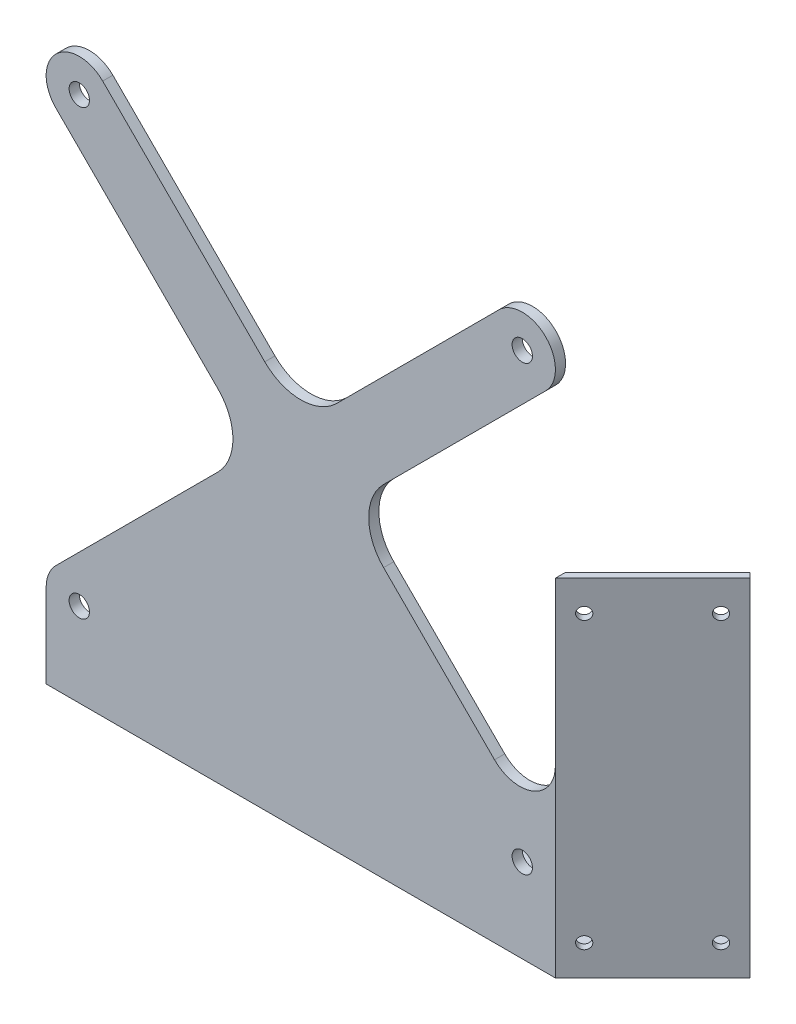
SolidWorks part; units mm, degrees
ref_plane "Plan de face" through (0, 0, 0) normal (0, 0, 1) x (1, 0, 0)
ref_plane "Plan de dessus" through (0, 0, 0) normal (0, 1, 0) x (1, 0, 0)
ref_plane "Plan de droite" through (0, 0, 0) normal (1, 0, 0) x (0, 0, -1)
sketch "Esquisse1" plane through (0, 0, 0) normal (0, 0, 1) x (1, 0, 0)
  line L1 (50, -55) -> (-50, -55)
  line L2 (50, -55) -> (50, 55)
  line L3 (50, 55) -> (-50, 55)
  line L4 (-50, -55) -> (-50, 55)
  line L5 (50, -55) -> (-50, 55) construction
  line L6 (50, 55) -> (-50, -55) construction
  point P0 (0, 0)
  dimension "D1" = 110
  dimension "D2" = 100
extrude "Boss.-Extru.1" add sketch "Esquisse1" along normal blind 2
sketch "Esquisse3" plane through (0, -55, 0) normal (0, -1, 0) x (1, 0, 0)
  line L0 (-50, 0) -> (50, 0)
  line L1 (-50, 0) -> (-50, -20)
  line L2 (50, 0) -> (50, -20)
  line L3 (-50, -20) -> (50, -20)
  dimension "D1" = 20
extrude "Boss.-Extru.2" add sketch "Esquisse3" against normal blind 3
sketch "Esquisse6" plane through (0, 0, 2) normal (0, 0, 1) x (1, 0, 0)
  line L0 (-43.5, 48.5) -> (-43.5, 55) construction
  line L1 (43.5, -38.5) -> (-43.5, -38.5) construction
  line L2 (43.5, -38.5) -> (43.5, 48.5) construction
  line L3 (43.5, 48.5) -> (-43.5, 48.5) construction
  line L4 (-43.5, -38.5) -> (-43.5, 48.5) construction
  line L5 (43.5, -38.5) -> (-43.5, 48.5) construction
  line L6 (43.5, 48.5) -> (-43.5, -38.5) construction
  line L7 (-43.5, 48.5) -> (-50, 48.5) construction
  line L8 (-50, 55) -> (-50, -55) construction
  line L9 (50, 55) -> (-50, 55) construction
  circle A0 centre (-43.5, 48.5) radius 2
  circle A1 centre (43.5, 48.5) radius 2
  circle A2 centre (-43.5, -38.5) radius 2
  circle A3 centre (43.5, -38.5) radius 2
  point P0 (0, 5)
  dimension "D1" = 4
  dimension "D2" = 87
extrude "Enlèv. mat.-Extru.1" cut sketch "Esquisse6" against normal through all
sketch "Esquisse7" plane through (0, 0, 2) normal (0, 0, 1) x (1, 0, 0)
  line L0 (-48.0962, 43.9038) -> (-9.1924, 5)
  line L1 (50, 55) -> (-50, 55) construction
  line L2 (-48.0962, -33.9038) -> (-9.1924, 5)
  line L3 (-50, 55) -> (-50, -55) construction
  line L4 (-48.0962, 43.9038) -> (-38.9038, 53.0962) construction
  line L5 (-38.9038, 53.0962) -> (0, 14.1924)
  line L6 (0, 14.1924) -> (0, 55)
  line L7 (0, 55) -> (-50, 55)
  line L8 (-50, 55) -> (-50, -38.5)
  arc A0 (-38.9038, 53.0962) -> (-48.0962, 43.9038) centre (-43.5, 48.5) ccw
  arc A1 (-48.0962, -33.9038) -> (-50, -38.5) centre (-43.5, -38.5) ccw
  line M14 (-50, 55) -> (-50, -55)
  line M17 (50, 55) -> (-50, 55)
  dimension "D1" = 50
extrude "Enlèv. mat.-Extru.2" cut sketch "Esquisse7" against normal through all contours A0 L5 L6 M17 | A1 L2 L0 A0 L8 | A0 L7 M14 region at (-13.6324, 41.4119, 2) region at (-48.5481, 53.5481, 2) region at (-36.4119, 5, 2)
mirror "Symétrie1" about plane through (0, 0, 0) normal (1, 0, 0) of "Enlèv. mat.-Extru.2"
fillet "Congé2" radius 10 3 edges at (9.1924, 5, 1) (0, 14.1924, 1) (-9.1924, 5, 1)
sketch "Esquisse8" plane through (0, -55, 0) normal (0, -1, 0) x (1, 0, 0)
  line L0 (50, 2) -> (69.0919, -17.0919)
  line L1 (69.0919, -17.0919) -> (66.1838, -20)
  line L2 (66.1838, -20) -> (50, -20)
  line L3 (50, -20) -> (50, 2)
  line L4 (-50, 2) -> (50, 2) construction
  point P8 (66.7978, -25.0828)
  dimension "D1" = 135
  dimension "D2" = 27
extrude "Boss.-Extru.3" add sketch "Esquisse8" against normal up to surface (3 mm away) up to face at (0, -52, -10)
hole_wizard "Fraisage pour vis à tête fraisée M51" positions "Esquisse4" profile "Esquisse5" countersink size "M5" standard "ISO" end condition through all
sketch "Esquisse4" plane through (0, -52, 0) normal (0, 1, 0) x (1, 0, 0)
  line L0 (-33, 12) -> (47, 12) construction
  line L2 (-50, 20) -> (66.1838, 20) construction
  line L3 (-50, 0) -> (-50, 20) construction
  point P0 (-33, 12)
  point P2 (47, 12)
  dimension "D1" = 80
  dimension "D2" = 8
  dimension "D3" = 17
sketch "Esquisse5" plane through (-33, -52, -12) normal (1, 0, 0) x (0, 0, 1)
  line L0 (0, 0) -> (0, 3)
  line L1 (0, 3) -> (2.75, 3)
  line L2 (2.75, 3) -> (2.75, 2.45)
  line L3 (2.75, 2.45) -> (5.2, 0)
  line L5 (5.2, 0) -> (0, 0)
  line L6 (-2.75, 2.45) -> (-5.2, 0) construction
  line L11 (0, -6.35) -> (0, 107.95) construction
  dimension "Diamètre du perçage jusqu'au prochain" = 5.5
  dimension "Profondeur du perçage jusqu'au prochain" = 3
  dimension "Diamètre du fraisage entrant" = 10.4
  dimension "Angle du fraisage entrant" = 90
sketch "Esquisse9" plane through (0, -52, 0) normal (0, 1, 0) x (1, 0, 0)
  line L0 (50, -2) -> (69.0919, 17.0919)
  line L1 (69.0919, 17.0919) -> (68.0919, 18.0919)
  line L2 (69.0919, 17.0919) -> (66.1838, 20) construction
  line L3 (68.0919, 18.0919) -> (50, 0)
  line L4 (50, 0) -> (50, -2)
extrude "Boss.-Extru.4" add sketch "Esquisse9" along normal blind 65
sketch "Esquisse10" plane through (0, 0, 2) normal (0, 0, 1) x (1, 0, 0)
  line L0 (48.0962, -33.9038) -> (50, -35.8076)
  line L1 (50, 13) -> (50, -38.5) construction
  line L2 (50, -35.8076) -> (50, -38.5)
  line L3 (50, -55) -> (50, -38.5) construction
  line L4 (50, -38.5) -> (48.0962, -33.9038)
  line L5 (48.0962, -33.9038) -> (16.2635, -2.0711) construction
  arc A0 (50, -38.5) -> (48.0962, -33.9038) centre (43.5, -38.5) ccw construction
extrude "Boss.-Extru.5" add sketch "Esquisse10" against normal up to surface (2 mm away) up to face at (-41.5, 48.5, 0)
fillet "Congé3" radius 7 1 edges at (50, -35.8076, 1)
sketch "Esquisse11" plane through (26, 0, 26) normal (0.7071, 0, 0.7071) x (0.7071, 0, -0.7071)
  line L0 (60.9411, 13) -> (60.9411, -55) construction
  line L1 (56.9411, -49) -> (37.9411, -49) construction
  line L2 (56.9411, -49) -> (56.9411, 7) construction
  line L3 (56.9411, 7) -> (37.9411, 7) construction
  line L4 (37.9411, -49) -> (37.9411, 7) construction
  line L5 (56.9411, -49) -> (37.9411, 7) construction
  line L6 (56.9411, 7) -> (37.9411, -49) construction
  line L7 (33.9411, 13) -> (60.9411, 13) construction
  point P0 (47.4411, -21)
  point P7 (60.9411, -21)
  point P8 (0, 0)
  point P11 (47.4411, 13)
  dimension "D1" = 56
  dimension "D2" = 19
hole_wizard "Dégagement M21" positions "Esquisse3D1" profile "Esquisse12" hole size "M2" standard "ISO" end condition through all
sketch3d "Esquisse3D1"
  point P0 (52.8284, 7, -0.8284)
  point P3 (66.2635, 7, -14.2635)
  point P6 (66.2635, -49, -14.2635)
  point P9 (52.8284, -49, -0.8284)
sketch "Esquisse12" plane through (52.8284, 7, -0.8284) normal (0, 1, 0) x (0.7071, 0, -0.7071)
  line L0 (0, 0) -> (0, 86.267)
  line L1 (0, 86.267) -> (1.2, 86.267)
  line L2 (1.2, 86.267) -> (1.2, 0)
  line L5 (1.2, 0) -> (0, 0)
  line L11 (0, -6.35) -> (0, 107.95) construction
  dimension "Diamètre du perçage jusqu'au prochain" = 2.4
  dimension "Profondeur du perçage jusqu'au prochain" = 86.267
fillet "Congé1" radius 2 2 edges at (0, -52, 0) (59.0459, -52, -9.0459)
